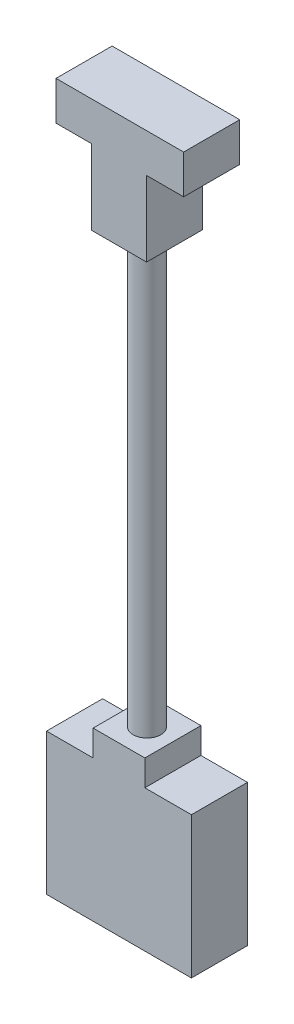
SolidWorks part; units mm, degrees
ref_plane "Front Plane" through (0, 0, 0) normal (0, 0, 1) x (1, 0, 0)
ref_plane "Top Plane" through (0, 0, 0) normal (0, 1, 0) x (1, 0, 0)
ref_plane "Right Plane" through (0, 0, 0) normal (1, 0, 0) x (0, 0, -1)
sketch "Sketch1" plane through (0, 0, 0) normal (0, 0, 1) x (1, 0, 0)
  line L52 (9.2772, 35.75) -> (13.3772, 35.75)
  line L53 (13.3772, 35.75) -> (13.3772, 27.05)
  line L54 (13.3772, 27.05) -> (19.7772, 27.05)
  line L55 (19.7772, 27.05) -> (19.7772, 35.75)
  line L56 (19.7772, 35.75) -> (24.0772, 35.75)
  line L57 (24.0772, 35.75) -> (24.0772, 40.25)
  line L58 (9.2772, 40.25) -> (9.2772, 35.75)
  line L59 (24.0772, 40.25) -> (9.2772, 40.25)
  line L70 (8.1772, -42.25) -> (24.9772, -42.25)
  line L71 (24.9772, -42.25) -> (24.9772, -25.85)
  line L72 (24.9772, -25.85) -> (19.5772, -25.85)
  line L73 (8.1772, -25.85) -> (8.1772, -42.25)
  line L83 (13.5772, -25.85) -> (8.1772, -25.85)
  line L89 (19.5772, -25.85) -> (19.5772, -22.85)
  line L90 (19.5772, -22.85) -> (13.5772, -22.85)
  line L91 (13.5772, -22.85) -> (13.5772, -25.85)
  point P16 (0, 0)
  point P17 (0, 0)
  point P18 (0, 0)
extrude "Boss-Extrude1" add sketch "Sketch1" along normal blind 6.5 contours L55 L56 L57 L59 L58 L52 L53 L54
extrude "Boss-Extrude2" add sketch "Sketch1<6>" along normal blind 6.5 separate body contours L71 L72 L89 L90 L91 L83 L73 L70
sketch "Sketch1<6>" plane through (0, 0, 0) normal (0, 0, 1) x (1, 0, 0) same geometry as "Sketch1"
sketch "Sketch2" plane through (0, 27.05, 0) normal (0, -1, 0) x (1, 0, 0)
  circle A0 centre (16.5772, 3.25) radius 1.6
  dimension "D1" = 3.2
extrude "Boss-Extrude3" add sketch "Sketch2" along normal blind 55
